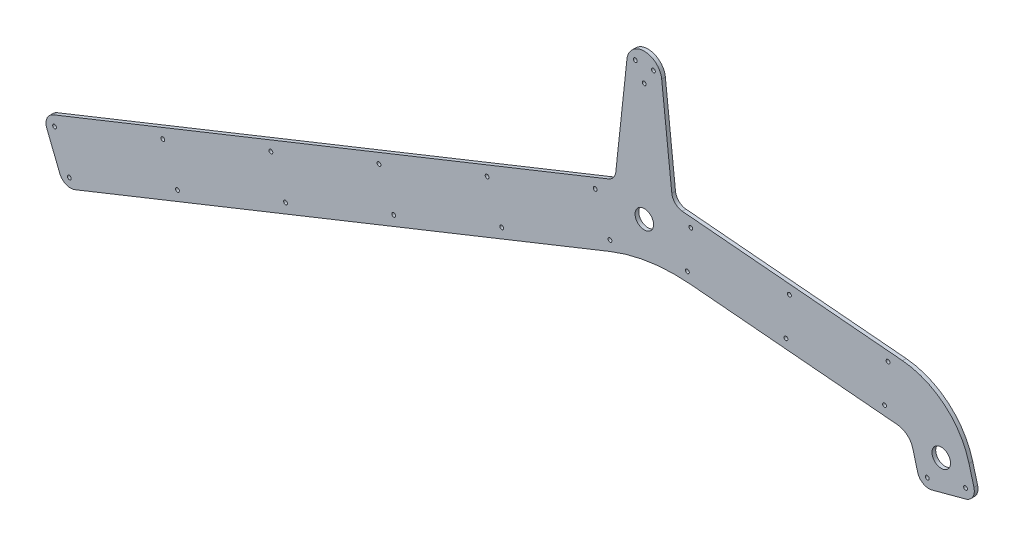
SolidWorks part; units mm, degrees
ref_plane "Front Plane" through (0, 0, 0) normal (0, 0, 1) x (1, 0, 0)
ref_plane "Top Plane" through (0, 0, 0) normal (0, 1, 0) x (1, 0, 0)
ref_plane "Right Plane" through (0, 0, 0) normal (1, 0, 0) x (0, 0, -1)
sketch "Sketch1" plane through (0, 0, 0) normal (0, 0, 1) x (1, 0, 0)
  line L0 (-325, 0) -> (325, 0) construction
  line L1 (-475, -190) -> (-325, 0) construction
  line L2 (325, 0) -> (475, -190) construction
  line L3 (-75, -190) -> (145, -190) construction
  line L4 (145, -190) -> (365, -190) construction
  line L5 (-25.1427, 16.8688) -> (-516.7815, -179.7868)
  line L6 (-516.7815, -179.7868) -> (-498.2119, -226.2106)
  line L7 (-498.2119, -226.2106) -> (-29.4264, -38.6964)
  line L8 (-507.4967, -202.9987) -> (-475, -190) construction
  line L9 (39.3556, -28.5387) -> (217.3643, -44.1124)
  line L11 (221.7221, 5.6973) -> (24.4857, 22.9533)
  line L12 (-25.1427, 16.8688) -> (-6.5731, -29.5551) construction
  line L13 (35, -190) -> (255, -49.8445) construction
  line L14 (255, -49.8445) -> (475, -190) construction
  line L15 (-25.1427, 16.8688) -> (-14.9133, 111.6102)
  line L16 (14.9133, 111.6102) -> (24.4857, 22.9533)
  line L17 (325, 0) -> (325, 80) construction
  line L18 (325, 80) -> (-325, 80) construction
  line L19 (-325, 80) -> (-325, 0) construction
  line L20 (24.4857, 22.9533) -> (20.1279, -26.8565) construction
  line L21 (-15.8579, -6.3432) -> (0, 0) construction
  line L22 (-25.1427, 16.8688) -> (24.4857, 22.9533) construction
  line L23 (230.5459, -55.173) -> (237.3223, -80.4632)
  line L24 (237.3223, -80.4632) -> (285.6186, -67.5222)
  line L25 (285.6186, -67.5222) -> (278.8422, -42.2321)
  line L26 (261.4705, -73.9927) -> (255, -49.8445) construction
  line L29 (0, 0) -> (22.3068, -1.9516) construction
  circle A0 centre (0, 0) radius 7.9375
  circle A1 centre (-475, -190) radius 110 construction
  circle A2 centre (35, -190) radius 110 construction
  circle A3 centre (475, -190) radius 110 construction
  circle A5 centre (255, -49.8445) radius 7.9375
  arc A6 (-14.9133, 111.6102) -> (14.9133, 111.6102) centre (0, 110) cw
  arc A7 (217.3643, -44.1124) -> (230.5459, -55.173) centre (216.057, -59.0553) cw
  arc A8 (221.7221, 5.6973) -> (278.8422, -42.2321) centre (216.057, -59.0553) cw
  arc A9 (-29.4264, -38.6964) -> (39.3556, -28.5387) centre (26.2822, -177.9679) cw
  point P11 (-475, -300)
  point P12 (0, 0)
  point P22 (0, 0)
  point P33 (196.6293, -32.5507)
  dimension "D1" = 15.875
  dimension "D4" = 220
  dimension "D9" = 115
  dimension "D12" = 30
  dimension "D16" = 15
  dimension "D17" = 150
  dimension "D2" = 325
  dimension "D3" = 650
  dimension "D5" = 300
  dimension "D6" = 150
  dimension "D7" = 50
  dimension "D8" = 35
  dimension "D10" = 80
  dimension "D11" = 30
  dimension "D13" = 25
  dimension "D14" = 5
  dimension "D15" = 75
extrude "Base" add sketch "Sketch1" along normal blind 3.175
fillet "Fillet1" radius 10 6 edges at (24.4857, 22.9533, 1.5875) (-25.1427, 16.8688, 1.5875) (237.3223, -80.4632, 1.5875) (285.6186, -67.5222, 1.5875) (-498.2119, -226.2106, 1.5875) (-516.7815, -179.7868, 1.5875)
sketch "Sketch2" plane through (0, 0, 3.175) normal (0, 0, 1) x (1, 0, 0)
  circle A0 centre (0, 110) radius 9 construction
  circle A1 centre (-7.7942, 114.5) radius 1.65
  circle A2 centre (7.7942, 114.5) radius 1.65
  circle A3 centre (0, 101) radius 1.65
  point P5 (22.4231, 127.1589)
  point P6 (0, 0)
  point P11 (0, 110)
  point P12 (-5.4781, 94.0647)
  point P13 (0, 110)
  point P14 (0, 100.9808)
  dimension "D2" = 3.3
  dimension "D3" = 18
  dimension "D1" = 3
extrude "Differential Attachment" cut sketch "Sketch2" against normal through all
sketch "Sketch3" plane through (0, 0, 3.175) normal (0, 0, 1) x (1, 0, 0)
  line L0 (-492.6411, -213.2119) -> (-496.5803, -222.4034) construction
  line L1 (-503.7828, -185.3576) -> (-512.9742, -181.4184) construction
  line L3 (-490.7841, -223.2395) -> (-493.7552, -215.8117) construction
  line L4 (-488.9272, -222.4967) -> (-29.4264, -38.6964) construction
  line L5 (-509.3536, -176.8156) -> (-506.3825, -184.2434) construction
  line L6 (-30.7255, 14.6356) -> (-507.4967, -176.0728) construction
  line L7 (-29.5169, -30.1163) -> (-42.1442, 1.4519) construction
  line L8 (-35.8305, -14.3322) -> (0, 0) construction
  line L9 (0, 0) -> (38.4438, -3.3634) construction
  line L10 (221.7221, 5.6973) -> (32.674, 22.2369) construction
  line L11 (39.9255, 13.5719) -> (36.9622, -20.2987) construction
  line L12 (239.3934, -76.876) -> (244.3934, -68.2157) construction
  line L13 (282.0314, -65.4511) -> (273.3712, -60.4511) construction
  line L14 (242.9792, -70.6652) -> (275.8207, -61.8654) construction
  line L15 (246.9816, -77.875) -> (275.9594, -70.1104) construction
  circle A0 centre (-506.3825, -184.2434) radius 1.65
  circle A1 centre (-493.7552, -215.8117) radius 1.65
  arc A3 (-501.9258, -216.9258) -> (-488.9272, -222.4967) centre (-492.6411, -213.2119) ccw construction
  arc A4 (-507.4967, -176.0728) -> (-513.0675, -189.0715) centre (-503.7828, -185.3576) ccw construction
  circle A5 centre (-400.9076, -178.6726) radius 1.65
  circle A6 centre (-413.5348, -147.1044) radius 1.65
  circle A7 centre (-308.0599, -141.5335) radius 1.65
  circle A8 centre (-320.6872, -109.9653) radius 1.65
  circle A9 centre (-215.2122, -104.3944) radius 1.65
  circle A10 centre (-227.8395, -72.8262) radius 1.65
  circle A11 centre (-122.3646, -67.2554) radius 1.65
  circle A12 centre (-134.9918, -35.6872) radius 1.65
  circle A13 centre (-29.5169, -30.1163) radius 1.65
  circle A14 centre (-42.1442, 1.4519) radius 1.65
  circle A15 centre (39.9255, 13.5719) radius 1.65
  circle A16 centre (36.9622, -20.2987) radius 1.65
  circle A17 centre (124.602, 6.1637) radius 1.65
  circle A18 centre (121.6387, -27.7069) radius 1.65
  circle A19 centre (209.2786, -1.2446) radius 1.65
  circle A20 centre (206.3153, -35.1152) radius 1.65
  circle A21 centre (242.9792, -70.6652) radius 1.65
  circle A22 centre (275.8207, -61.8654) radius 1.65
  arc A23 (234.7341, -70.8039) -> (246.9816, -77.875) centre (244.3934, -68.2157) ccw construction
  arc A24 (275.9594, -70.1104) -> (283.0304, -57.863) centre (273.3712, -60.4511) ccw construction
  point P53 (38.4438, -3.3634)
  point P81 (40.497, 19.4231)
  dimension "D2" = 3.3
  dimension "D1" = 8
  dimension "D5" = 100
  dimension "D6" = 85
  dimension "D3" = 6
  dimension "D4" = 3
extrude "Strut Holes" cut sketch "Sketch3" against normal through all
